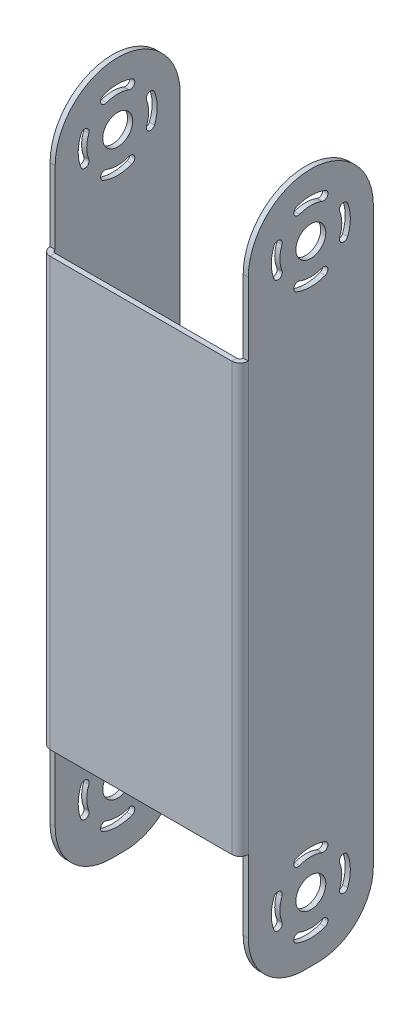
SolidWorks part; units mm, degrees
note: The reader was unsure of these and kept them because the rebuilt part matched: flange length of "邊線-凸緣2".
ref_plane "前基準面" through (0, 0, 0) normal (0, 0, 1) x (1, 0, 0)
ref_plane "上基準面" through (0, 0, 0) normal (0, 1, 0) x (1, 0, 0)
ref_plane "右基準面" through (0, 0, 0) normal (1, 0, 0) x (0, 0, -1)
sketch "草圖1" plane through (0, 0, 0) normal (0, 0, 1) x (1, 0, 0)
  line L1 (-51.0362, 43.4203) -> (-7.0362, 43.4203)
  line L2 (-51.0362, 43.4203) -> (-51.0362, -56.5797)
  line L3 (-51.0362, -56.5797) -> (-7.0362, -56.5797)
  line L4 (-7.0362, 43.4203) -> (-7.0362, -56.5797)
  dimension "D1" = 44
  dimension "D2" = 100
base flange "基材-凸緣1" sketch "草圖1" thickness 1.2 reverse thickness direction no parameters "D1"=0.7366
edge flange "邊線-凸緣2" sketch "草圖20" flange profiles "草圖20", "草圖21" flange angle 90 flange length 30 flange position material outside bend radius 0.7366 thickness 1.2 relief rectangular parameters "D6"=10, "D8"=1
sketch "草圖20" plane through (-7.0362, 0, -1.2) normal (-1, 0, 0) x (0, 1, 0)
  line L1 (43.4203, 0) -> (-56.5797, 0) construction
  line L2 (-56.5797, 0) -> (-56.5797, 30)
  line L3 (-56.5797, 30) -> (43.4203, 30)
  line L4 (43.4203, 30) -> (43.4203, 0)
  line L5 (43.4203, 0) -> (-56.5797, 0)
sketch "草圖21" plane through (-51.0362, 0, -1.2) normal (1, 0, 0) x (0, -1, 0)
  line L0 (56.5797, 0) -> (-43.4203, 0) construction
  line L1 (56.5797, 0) -> (-43.4203, 0)
  line L2 (56.5797, 0) -> (56.5797, 30)
  line L3 (56.5797, 30) -> (-43.4203, 30)
  line L4 (-43.4203, 30) -> (-43.4203, 0)
bend "邊線彎折3" bend radius 0.7366 bend angle 90 parameters "D5"=1
bend "邊線彎折4" bend radius 0.7366 bend angle 90 parameters "D5"=2
sketch "草圖38" plane through (-5.8362, 0, 0) normal (1, 0, 0) x (0, 0, -1)
  line L0 (31.2, 43.4203) -> (31.2, -56.5797) construction
  line L1 (1.9366, 43.4203) -> (31.2, 43.4203)
  line L2 (1.9366, 43.4203) -> (1.9366, 60.4203)
  line L4 (31.2, 43.4203) -> (31.2, 60.4203)
  arc A0 (31.2, 60.4203) -> (1.9366, 60.4203) centre (16.5683, 60.4203) ccw
extrude "填料-伸長1" add sketch "草圖38" against normal blind 1.2
sketch "草圖41" plane through (-52.2362, 0, 0) normal (-1, 0, 0) x (0, 0, 1)
  line L0 (-31.2, -56.5797) -> (-31.2, 43.4203) construction
  line L1 (-1.9366, 43.4203) -> (-31.2, 43.4203)
  line L2 (-1.9366, 43.4203) -> (-1.9366, 60.4203)
  line L4 (-31.2, 43.4203) -> (-31.2, 60.4203)
  arc A0 (-1.9366, 60.4203) -> (-31.2, 60.4203) centre (-16.5683, 60.4203) ccw
extrude "填料-伸長2" add sketch "草圖41" against normal blind 1.2
sketch "草圖44" plane through (-52.2362, 0, 0) normal (-1, 0, 0) x (0, 0, 1)
  line L0 (-25.8183, 60.4203) -> (6.8924, 60.4203) construction
  line L1 (-16.5683, 78.7367) -> (-16.5683, 38.118) construction
  line L2 (-16.5683, 60.4203) -> (-39.7817, 39.3007) construction
  line L3 (-39.7817, 39.3007) -> (2.2161, 77.5103) construction
  line L4 (-16.5683, 60.4203) -> (-39.7817, 77.5103) construction
  line L5 (-39.7817, 77.5103) -> (12.1185, 39.3007) construction
  arc A0 (-13.2047, 69.037) -> (-19.9319, 69.037) centre (-16.5683, 60.4203) ccw
  circle A1 centre (-16.5683, 60.4203) radius 3.5
  arc A2 (-13.9319, 67.1739) -> (-19.2047, 67.1739) centre (-16.5683, 60.4203) ccw
  arc A3 (-7.9515, 57.0566) -> (-7.9515, 63.7839) centre (-16.5683, 60.4203) ccw
  arc A4 (-13.9319, 67.1739) -> (-13.2047, 69.037) centre (-13.5683, 68.1055) ccw
  arc A5 (-19.9319, 69.037) -> (-19.2047, 67.1739) centre (-19.5683, 68.1055) ccw
  arc A6 (-9.8146, 57.7839) -> (-9.8146, 63.0566) centre (-16.5683, 60.4203) ccw
  arc A7 (-7.9515, 63.7839) -> (-9.8146, 63.0566) centre (-8.8831, 63.4203) ccw
  circle A8 centre (-16.5683, 60.4203) radius 9.25 construction
  arc A9 (-9.8146, 57.7839) -> (-7.9515, 57.0566) centre (-8.8831, 57.4203) ccw
  circle A10 centre (-16.5683, 60.4203) radius 7.25 construction
  arc A11 (-19.9319, 51.8035) -> (-13.2047, 51.8035) centre (-16.5683, 60.4203) ccw
  arc A12 (-19.2047, 53.6666) -> (-13.9319, 53.6666) centre (-16.5683, 60.4203) ccw
  arc A13 (-13.2047, 51.8035) -> (-13.9319, 53.6666) centre (-13.5683, 52.7351) ccw
  arc A14 (-19.2047, 53.6666) -> (-19.9319, 51.8035) centre (-19.5683, 52.7351) ccw
  arc A15 (-25.1851, 63.7839) -> (-25.1851, 57.0566) centre (-16.5683, 60.4203) ccw
  arc A16 (-23.322, 63.0566) -> (-23.322, 57.7839) centre (-16.5683, 60.4203) ccw
  arc A17 (-25.1851, 57.0566) -> (-23.322, 57.7839) centre (-24.2535, 57.4203) ccw
  arc A18 (-23.322, 63.0566) -> (-25.1851, 63.7839) centre (-24.2535, 63.4203) ccw
  point P3 (-8.3183, 60.4203)
  point P14 (-16.5683, 60.4203)
  point P17 (-7.7225, 63.1247)
  point P28 (-9.6351, 62.54)
  point P45 (-16.5683, 60.4203)
  dimension "D1" = 2
  dimension "D2" = 18.5
  dimension "D6" = 7
  dimension "D4" = 3
  dimension "D5" = 3
  dimension "D3" = 4
extrude "除料-伸長3" cut sketch "草圖44" against normal through all contours A1 | A3 A7 A6 A9 | A2 A5 A0 A4 | A16 A17 A15 A18 | A12 A13 A11 A14 normal cut yes
sketch "草圖45" plane through (0, -56.5797, 0) normal (0, -1, 0) x (1, 0, 0)
  line L0 (-51.0362, -31.2) -> (-51.0362, -1.9366) construction
  line L1 (-51.0362, -1.9366) -> (-52.2362, -1.9366) construction
  line L2 (-52.2362, -1.9366) -> (-52.2362, -31.2) construction
  line L3 (-52.2362, -31.2) -> (-51.0362, -31.2) construction
  line L4 (-5.8362, -31.2) -> (-5.8362, -1.9366) construction
  line L5 (-5.8362, -1.9366) -> (-7.0362, -1.9366) construction
  line L6 (-7.0362, -1.9366) -> (-7.0362, -31.2) construction
  line L7 (-7.0362, -31.2) -> (-5.8362, -31.2) construction
  line L8 (-51.0362, -31.2) -> (-51.0362, -1.9366)
  line L9 (-51.0362, -1.9366) -> (-52.2362, -1.9366)
  line L10 (-52.2362, -1.9366) -> (-52.2362, -31.2)
  line L11 (-52.2362, -31.2) -> (-51.0362, -31.2)
  line L12 (-5.8362, -31.2) -> (-5.8362, -1.9366)
  line L13 (-5.8362, -1.9366) -> (-7.0362, -1.9366)
  line L14 (-7.0362, -1.9366) -> (-7.0362, -31.2)
  line L15 (-7.0362, -31.2) -> (-5.8362, -31.2)
extrude "填料-伸長3" add sketch "草圖45" along normal blind 30
sketch "草圖48" plane through (-52.2362, 0, 0) normal (-1, 0, 0) x (0, 0, 1)
  line L0 (-16.5683, -86.5797) -> (-16.5683, -54.522) construction
  line L1 (-1.9366, -86.5797) -> (-31.2, -86.5797) construction
  line L2 (-1.9366, -71.5797) -> (-31.2, -71.5797) construction
  line L3 (-1.9366, -86.5797) -> (-1.9366, -56.5797) construction
  line L4 (-31.2, -86.5797) -> (-31.2, 60.4203) construction
  circle A0 centre (-16.5683, -71.5797) radius 3.5
  arc A1 (-7.9515, -74.9434) -> (-7.9515, -68.2161) centre (-16.5683, -71.5797) ccw
  arc A2 (-19.2047, -78.3334) -> (-13.9319, -78.3334) centre (-16.5683, -71.5797) ccw
  arc A3 (-7.9515, -68.2161) -> (-9.8146, -68.9434) centre (-8.8831, -68.5797) ccw
  arc A4 (-9.8146, -74.2161) -> (-7.9515, -74.9434) centre (-8.8831, -74.5797) ccw
  arc A5 (-13.2047, -80.1965) -> (-13.9319, -78.3334) centre (-13.5683, -79.2649) ccw
  arc A6 (-9.8146, -74.2161) -> (-9.8146, -68.9434) centre (-16.5683, -71.5797) ccw
  arc A7 (-19.9319, -80.1965) -> (-13.2047, -80.1965) centre (-16.5683, -71.5797) ccw
  arc A8 (-19.2047, -78.3334) -> (-19.9319, -80.1965) centre (-19.5683, -79.2649) ccw
  arc A9 (-23.322, -68.9434) -> (-23.322, -74.2161) centre (-16.5683, -71.5797) ccw
  arc A10 (-25.1851, -74.9434) -> (-23.322, -74.2161) centre (-24.2535, -74.5797) ccw
  arc A11 (-25.1851, -68.2161) -> (-25.1851, -74.9434) centre (-16.5683, -71.5797) ccw
  arc A12 (-23.322, -68.9434) -> (-25.1851, -68.2161) centre (-24.2535, -68.5797) ccw
  arc A13 (-13.9319, -64.8261) -> (-19.2047, -64.8261) centre (-16.5683, -71.5797) ccw
  arc A14 (-19.9319, -62.963) -> (-19.2047, -64.8261) centre (-19.5683, -63.8945) ccw
  arc A15 (-13.2047, -62.963) -> (-19.9319, -62.963) centre (-16.5683, -71.5797) ccw
  arc A16 (-13.9319, -64.8261) -> (-13.2047, -62.963) centre (-13.5683, -63.8945) ccw
  point P39 (-16.5683, -71.5797)
  dimension "D1" = 7
  dimension "D2" = 18.5
  dimension "D3" = 4
  dimension "D4" = 2
  dimension "D5" = 2
  dimension "D6" = 6
  dimension "D7" = 3
extrude "除料-伸長4" cut sketch "草圖48" against normal through all normal cut yes
fillet "圓角1" radius 13 4 edges at (-51.6362, -86.5797, -1.9366) (-6.4362, -86.5797, -1.9366) (-6.4362, -86.5797, -31.2) (-51.6362, -86.5797, -31.2)
sketch "彎折-線1" plane through (0, 0, 0) normal (0, 1, 0) x (1, 0, 0)
sketch "邊界方塊1" plane through (0, 0, 0) normal (0, 1, 0) x (1, 0, 0)
sheet metal parameters "鈑金(1)" thickness 1.2 parameters "D1"=0.7366
flat pattern "平板-型式(1)" [suppressed]
sketch "彎折-線2" plane through (0, 0, 0) normal (0, 1, 0) x (1, 0, 0)
sketch "邊界方塊2" [suppressed] plane through (0, 0, 0) normal (0, 1, 0) x (1, 0, 0)
sheet metal parameters "鈑金(3)" thickness 1.2 parameters "D1"=0.7366
flat pattern "平板-型式(1)" [suppressed]
sketch "彎折-線4" plane through (0, 0, 0) normal (0, 1, 0) x (1, 0, 0)
sketch "邊界方塊4" [suppressed] plane through (0, 0, 0) normal (0, 1, 0) x (1, 0, 0)
bend of the flat pattern "平板-<邊線彎折3>1"
bend of the flat pattern "平板-<邊線彎折4>1"
sheet metal parameters "鈑金(6)" thickness 1.2 parameters "D1"=0.7366
flat pattern "平板-型式(1)" [suppressed]
sketch "彎折-線7" plane through (0, 0, 0) normal (0, 1, 0) x (1, 0, 0)
sketch "邊界方塊7" [suppressed] plane through (0, 0, 0) normal (0, 1, 0) x (1, 0, 0)
bend of the flat pattern "平板-<邊線彎折3>4"
bend of the flat pattern "平板-<邊線彎折4>4"
sheet metal parameters "鈑金(7)" thickness 1.2 parameters "D1"=0.7366
flat pattern "平板-型式(1)" [suppressed]
sketch "彎折-線8" plane through (0, 0, 0) normal (0, 1, 0) x (1, 0, 0)
sketch "邊界方塊8" [suppressed] plane through (0, 0, 0) normal (0, 1, 0) x (1, 0, 0)
bend of the flat pattern "平板-<邊線彎折3>5"
bend of the flat pattern "平板-<邊線彎折4>5"
sheet metal parameters "鈑金(9)" thickness 1.2 parameters "D1"=0.7366
flat pattern "平板-型式(1)" [suppressed]
sketch "彎折-線10" plane through (0, 0, 0) normal (0, 1, 0) x (1, 0, 0)
sketch "邊界方塊10" [suppressed] plane through (0, 0, 0) normal (0, 1, 0) x (1, 0, 0)
bend of the flat pattern "平板-<邊線彎折3>7"
bend of the flat pattern "平板-<邊線彎折4>7"
sheet metal parameters "鈑金(15)" thickness 1.2 parameters "D1"=0.7366
flat pattern "平板-型式(1)" [suppressed]
sketch "彎折-線11" plane through (0, 0, 0) normal (0, 1, 0) x (1, 0, 0)
sketch "邊界方塊11" [suppressed] plane through (0, 0, 0) normal (0, 1, 0) x (1, 0, 0)
bend of the flat pattern "平板-<邊線彎折3>8"
bend of the flat pattern "平板-<邊線彎折4>8"
sheet metal parameters "鈑金(16)" thickness 1.2 parameters "D1"=0.7366
flat pattern "平板-型式(1)" [suppressed]
sketch "彎折-線12" plane through (0, 0, 0) normal (0, 1, 0) x (1, 0, 0)
sketch "邊界方塊12" [suppressed] plane through (0, 0, 0) normal (0, 1, 0) x (1, 0, 0)
bend of the flat pattern "平板-<邊線彎折3>9"
bend of the flat pattern "平板-<邊線彎折4>9"
